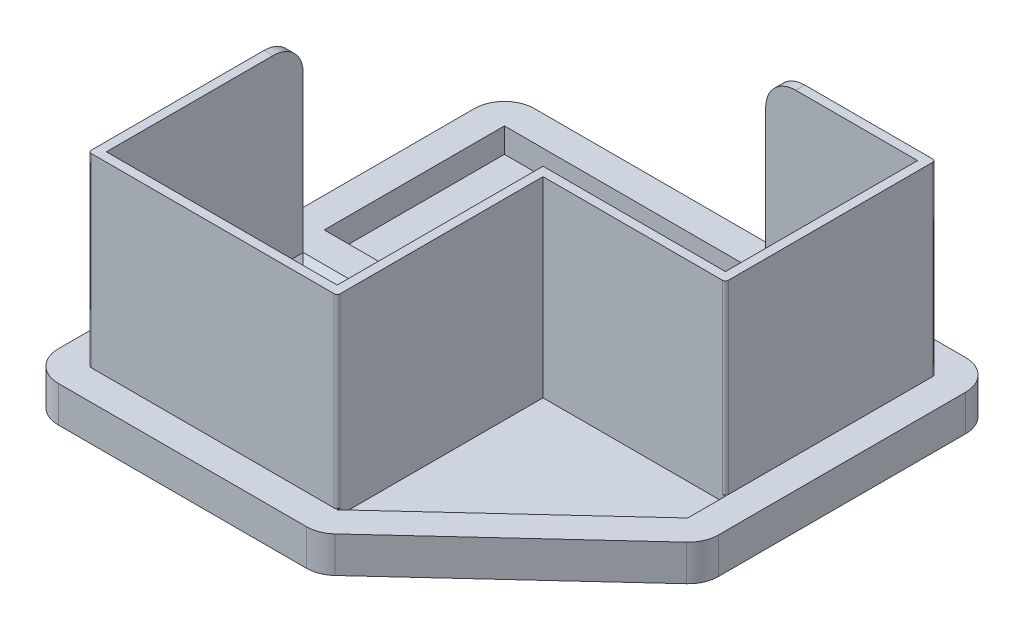
SolidWorks part; units mm, degrees
material "Maple"
ref_plane "Front Plane" through (0, 0, 0) normal (0, 0, 1) x (1, 0, 0)
ref_plane "Top Plane" through (0, 0, 0) normal (0, 1, 0) x (1, 0, 0)
ref_plane "Right Plane" through (0, 0, 0) normal (1, 0, 0) x (0, 0, -1)
sketch "Sketch1" plane through (0, 0, 0) normal (0, 1, 0) x (1, 0, 0)
  line L3 (818, 792.7) -> (0, 792.7)
  line L4 (0, 792.7) -> (0, 0)
  line L5 (50, 742.7) -> (450, 742.7) construction
  line L6 (450, 742.7) -> (450, 442.7) construction
  line L7 (450, 442.7) -> (50, 442.7) construction
  line L8 (50, 442.7) -> (50, 742.7) construction
  line L9 (268, 550) -> (0, 127.891) construction
  line L10 (268, 550) -> (705.1461, 792.7) construction
  line L11 (268, 550) -> (768, 550) construction
  line L12 (268, 550) -> (268, 50) construction
  line L13 (268, 550) -> (610.9947, 186.1942) construction
  line L14 (482.772, 0) -> (818, 309.0058)
  line L15 (610.9947, 186.1942) -> (409, 0) construction
  line L16 (818, 792.7) -> (818, 309.0058)
  line L17 (482.772, 0) -> (0, 0)
  circle A0 centre (268, 550) radius 80 construction
  arc A1 (0, 127.891) -> (705.1461, 792.7) centre (268, 550) ccw construction
  dimension "D7" = 160
  dimension "D8" = 500
  dimension "D1" = 400
  dimension "D2" = 300
  dimension "D3" = 50
  dimension "D4" = 50
  dimension "D5" = 182
  dimension "D6" = 107.3
  dimension "D9" = 50
  dimension "D10" = 50
  dimension "D11" = 50
  dimension "D12" = 0
extrude "Boss-Extrude1" add sketch "Sketch1" along normal blind 60
sketch "Sketch3" plane through (0, 60, 0) normal (0, 1, 0) x (1, 0, 0)
  line L0 (818, 792.7) -> (0, 792.7) construction
  line L1 (50, 742.7) -> (450, 742.7)
  line L2 (50, 742.7) -> (50, 442.7)
  line L3 (50, 442.7) -> (450, 442.7)
  line L4 (450, 742.7) -> (450, 442.7)
  line L5 (0, 792.7) -> (0, 0) construction
  line L6 (269, 550) -> (0, 128.5276) construction
  line L7 (269, 550) -> (706.1461, 792.7) construction
  line L8 (168.6051, 392.7) -> (500, 392.7)
  line L9 (500, 392.7) -> (500, 678.2493)
  line L10 (168.6051, 392.7) -> (50, 392.7)
  line L11 (50, 392.7) -> (50, 50)
  line L12 (50, 50) -> (464.2896, 50)
  line L13 (464.2896, 50) -> (768, 329.9535)
  line L14 (768, 329.9535) -> (768, 742.7)
  line L15 (768, 742.7) -> (500, 742.7)
  line L16 (500, 742.7) -> (500, 678.2493)
  line L17 (818, 309.0058) -> (818, 792.7) construction
  line L18 (0, 0) -> (482.772, 0) construction
  line L19 (482.772, 0) -> (818, 309.0058) construction
  circle A0 centre (269, 550) radius 80 construction
  arc A1 (0, 128.5276) -> (706.1461, 792.7) centre (269, 550) ccw construction
  dimension "D7" = 500
  dimension "D8" = 160
  dimension "D1" = 400
  dimension "D2" = 300
  dimension "D3" = 50
  dimension "D4" = 50
  dimension "D5" = 181
  dimension "D6" = 107.3
  dimension "D9" = 50
  dimension "D10" = 50
  dimension "D11" = 50
  dimension "D12" = 50
  dimension "D13" = 50
  dimension "D14" = 50
  dimension "D15" = 0
extrude "Cut-Extrude1" cut sketch "Sketch3" against normal blind 41
sketch "Sketch4" plane through (0, 19, 0) normal (0, 1, 0) x (1, 0, 0)
  line L0 (464.2896, 50) -> (464.2896, 392.7)
  line L1 (500, 392.7) -> (50, 392.7) construction
  line L2 (464.2896, 392.7) -> (449.2896, 392.7)
  line L3 (500, 392.7) -> (50, 392.7) construction
  line L4 (449.2896, 392.7) -> (449.2896, 65)
  line L5 (449.2896, 65) -> (65, 65)
  line L6 (65, 65) -> (65, 392.7)
  line L7 (65, 392.7) -> (50, 392.7)
  line L8 (50, 392.7) -> (50, 50)
  line L9 (50, 50) -> (464.2896, 50)
  dimension "D1" = 15
  dimension "D2" = 15
  dimension "D3" = 15
extrude "Boss-Extrude2" add sketch "Sketch4" along normal blind 350
sketch "Sketch5" plane through (0, 19, 0) normal (0, 1, 0) x (1, 0, 0)
  line L1 (768, 329.9535) -> (768, 742.7) construction
  line L2 (768, 392.7) -> (768, 742.7)
  line L3 (768, 742.7) -> (500, 742.7)
  line L4 (500, 742.7) -> (500, 727.7)
  line L5 (500, 742.7) -> (500, 392.7) construction
  line L6 (500, 727.7) -> (753, 727.7)
  line L7 (753, 727.7) -> (753, 407.7)
  line L8 (753, 407.7) -> (500, 407.7)
  line L10 (768, 392.7) -> (449.2896, 392.7)
  line L11 (449.2896, 392.7) -> (449.2896, 407.7)
  line L12 (449.2896, 407.7) -> (500, 407.7)
  dimension "D1" = 15
  dimension "D2" = 15
  dimension "D3" = 15
extrude "Boss-Extrude3" add sketch "Sketch5" along normal blind 350
fillet "Fillet1" radius 50 2 edges at (57.5, 369, -392.7) (500, 369, -735.2)
fillet "Fillet2" radius 50 5 edges at (818, 30, -792.7) (0, 30, 0) (0, 30, -792.7) (818, 30, -309.0058) (482.772, 30, 0)
sketch "Sketch6" plane through (0, 19, 0) normal (0, 1, 0) x (1, 0, 0)
  line L0 (768, 392.7) -> (464.2896, 392.7)
  line L1 (753, 407.7) -> (500, 407.7)
  line L2 (753, 407.7) -> (753, 727.7)
  line L3 (753, 727.7) -> (500, 727.7)
  line L4 (500, 407.7) -> (500, 727.7)
  line L5 (449.2896, 392.7) -> (65, 392.7)
  line L6 (449.2896, 392.7) -> (449.2896, 65)
  line L7 (449.2896, 65) -> (65, 65)
  line L8 (65, 392.7) -> (65, 65)
  line L9 (464.2896, 392.7) -> (464.2896, 50)
  line L10 (464.2896, 50) -> (768, 329.9535)
  line L11 (768, 329.9535) -> (768, 392.7)
extrude "Boss-Extrude4" add sketch "Sketch6" along normal blind 31
chamfer "Chamfer5" distance 10 angle 45 8 edges at (257.1448, 50, -65) (65, 50, -228.85) (257.1448, 50, -392.7) (449.2896, 50, -228.85) (626.5, 50, -407.7) (500, 50, -567.7) (626.5, 50, -727.7) (753, 50, -567.7)
fillet "Fillet3" radius 5 4 edges at (50, 214.5, -50) (464.2896, 214.5, -50) (768, 214.5, -392.7) (768, 214.5, -742.7)
